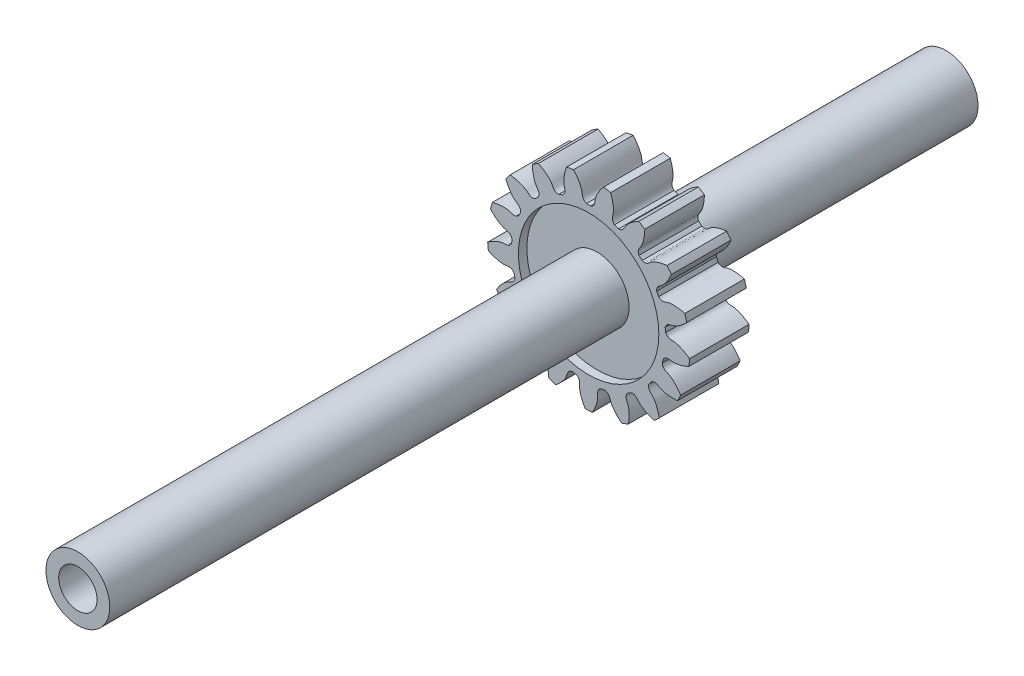
SolidWorks part; units mm, degrees
ref_plane "前视基准面" through (0, 0, 0) normal (0, 0, 1) x (1, 0, 0)
ref_plane "上视基准面" through (0, 0, 0) normal (0, 1, 0) x (1, 0, 0)
ref_plane "右视基准面" through (0, 0, 0) normal (1, 0, 0) x (0, 0, -1)
sketch "草图1" plane through (0, 0, 0) normal (0, 0, 1) x (1, 0, 0)
  circle A0 centre (0, 0) radius 23.75
extrude "凸台-拉伸1" add sketch "草图1" along normal blind 14
ref_axis "基准轴1" through (0, 0, 14) along (0, 0, -1)
sketch "草图2" plane through (0, 0, 0) normal (0, 0, 1) x (1, 0, 0)
  line L0 (0, 0) -> (0, 23.75) construction
  circle A0 centre (0, 0) radius 23.75 construction
  arc A1 (0.5042, 18.118) -> (-0.5042, 18.118) centre (0, 0) ccw
  arc A2 (7.7891, 26.8518) -> (-7.7891, 26.8518) centre (0, 0) ccw
  spline S0 degree 3 poles (0.5042, 18.118) (1.5697, 18.5621) (1.4155, 19.387) (1.5958, 20.1621) (1.6124, 20.2279) (1.6325, 20.301) (1.6564, 20.3815) (1.6842, 20.469) (1.7164, 20.5635) (1.7532, 20.6649) (1.7948, 20.773) (1.8417, 20.8876) (1.894, 21.0086) (1.952, 21.1357) (2.016, 21.2689) (2.0862, 21.408) (2.163, 21.5526) (2.2465, 21.7027) (2.337, 21.8579) (2.4348, 22.0182) (2.54, 22.1832) (2.653, 22.3527) (2.7739, 22.5264) (2.9029, 22.7042) (3.0403, 22.8857) (3.1862, 23.0708) (3.3408, 23.259) (3.5044, 23.4502) (3.6771, 23.644) (3.8591, 23.8402) (4.0505, 24.0385) (4.2515, 24.2385) (4.4622, 24.44) (4.6828, 24.6427) (4.9134, 24.8461) (5.1541, 25.0501) (5.405, 25.2543) (5.6663, 25.4584) (5.9379, 25.6619) (6.2201, 25.8647) (6.5129, 26.0663) (6.8163, 26.2664) (7.2396, 26.5336) (7.5664, 26.7263) (7.7891, 26.8518) knots 0 0 0 0 0.193883 0.199024 0.204851 0.211363 0.21856 0.226443 0.235011 0.244265 0.254205 0.264829 0.27614 0.288136 0.300817 0.314184 0.328236 0.342973 0.358397 0.374505 0.391299 0.408779 0.426944 0.445795 0.465331 0.485552 0.506459 0.528051 0.550329 0.573293 0.596941 0.621276 0.646296 0.672001 0.698392 0.725468 0.753229 0.781677 0.810809 0.840627 0.871131 0.90232 0.934195 1 1 1 1
  spline S1 degree 3 poles (-0.5042, 18.118) (-1.5697, 18.5621) (-1.4155, 19.387) (-1.5958, 20.1621) (-1.6124, 20.2279) (-1.6325, 20.301) (-1.6564, 20.3815) (-1.6842, 20.469) (-1.7164, 20.5635) (-1.7532, 20.6649) (-1.7948, 20.773) (-1.8417, 20.8876) (-1.894, 21.0086) (-1.952, 21.1357) (-2.016, 21.2689) (-2.0862, 21.408) (-2.163, 21.5526) (-2.2465, 21.7027) (-2.337, 21.8579) (-2.4348, 22.0182) (-2.54, 22.1832) (-2.653, 22.3527) (-2.7739, 22.5264) (-2.9029, 22.7042) (-3.0403, 22.8857) (-3.1862, 23.0708) (-3.3408, 23.259) (-3.5044, 23.4502) (-3.6771, 23.644) (-3.8591, 23.8402) (-4.0505, 24.0385) (-4.2515, 24.2385) (-4.4622, 24.44) (-4.6828, 24.6427) (-4.9134, 24.8461) (-5.1541, 25.0501) (-5.405, 25.2543) (-5.6663, 25.4584) (-5.9379, 25.6619) (-6.2201, 25.8647) (-6.5129, 26.0663) (-6.8163, 26.2664) (-7.2396, 26.5336) (-7.5664, 26.7263) (-7.7891, 26.8518) knots 0 0 0 0 0.193883 0.199024 0.204851 0.211363 0.21856 0.226443 0.235011 0.244265 0.254205 0.264829 0.27614 0.288136 0.300817 0.314184 0.328236 0.342973 0.358397 0.374505 0.391299 0.408779 0.426944 0.445795 0.465331 0.485552 0.506459 0.528051 0.550329 0.573293 0.596941 0.621276 0.646296 0.672001 0.698392 0.725468 0.753229 0.781677 0.810809 0.840627 0.871131 0.90232 0.934195 1 1 1 1
extrude "切除-拉伸1" cut sketch "草图2" along normal through all
pattern_circular "阵列(圆周)1" count 17 over 360 about axis through (0, 0, 14) along (0, 0, -1) of "切除-拉伸1"
sketch "草图3" plane through (0, 0, 0) normal (0, 0, 1) x (1, 0, 0)
  circle A0 centre (0, 0) radius 21.25 construction
  dimension "Dn" = 42.5
sketch "草图4" plane through (0, 0, 14) normal (0, 0, 1) x (1, 0, 0)
  circle A0 centre (0, 0) radius 5
  dimension "D1" = 10
extrude "切除-拉伸2" cut sketch "草图4" against normal through all
sketch "草图5" plane through (0, 0, 14) normal (0, 0, 1) x (1, 0, 0)
  circle A0 centre (0, 0) radius 4.5
  circle A1 centre (0, 0) radius 7.5
  dimension "D1" = 15
  dimension "D2" = 9
extrude "凸台-拉伸2" add sketch "草图5" along normal blind 120
sketch "草图6" plane through (0, 0, 0) normal (0, 0, -1) x (-1, 0, 0)
  circle A0 centre (0, 0) radius 4.5
  circle A1 centre (0, 0) radius 7.5
  dimension "D1" = 15
  dimension "D2" = 9
extrude "凸台-拉伸3" add sketch "草图6" along normal blind 70
sketch "草图7" plane through (0, 0, 0) normal (0, 0, -1) x (-1, 0, 0)
  circle A0 centre (0, 0) radius 16.5
  dimension "D1" = 33
extrude "切除-拉伸3" cut sketch "草图7" against normal blind 2
sketch "草图8" plane through (0, 0, 14) normal (0, 0, 1) x (1, 0, 0)
  circle A0 centre (0, 0) radius 16.5
  dimension "D1" = 33
extrude "切除-拉伸4" cut sketch "草图8" against normal blind 2
sketch "草图9" plane through (0, 0, 0) normal (0, 0, 1) x (1, 0, 0)
  circle A0 centre (0, 0) radius 10
  circle A1 centre (0, 0) radius 12.5
sketch "草图10" plane through (0, 0, -70) normal (0, 0, -1) x (-1, 0, 0)
  circle A0 centre (0, 0) radius 10
sketch "草图11" plane through (0, 0, 14) normal (0, 0, -1) x (-1, 0, 0)
  circle A0 centre (0, 0) radius 12.5
  circle A1 centre (0, 0) radius 10
sketch "草图12" plane through (0, 0, 2) normal (0, 0, -1) x (-1, 0, 0)
  circle A0 centre (0, 0) radius 4.5
  circle A1 centre (0, 0) radius 7.5
  dimension "D1" = 15
extrude "凸台-拉伸7" add sketch "草图12" along normal up to next (2 mm away)
sketch "草图13" plane through (0, 0, 12) normal (0, 0, 1) x (1, 0, 0)
  circle A0 centre (0, 0) radius 5
sketch "草图14" plane through (0, 0, 12) normal (0, 0, 1) x (1, 0, 0)
  circle A0 centre (0, 0) radius 5
  circle A1 centre (0, 0) radius 7.5
  dimension "D1" = 15
extrude "凸台-拉伸8" add sketch "草图13" against normal up to surface (10 mm away) up to face at (-4.5, 0, 2)
extrude "凸台-拉伸9" add sketch "草图14" along normal up to next (2 mm away)
sketch "草图15" plane through (0, 0, 134) normal (0, 0, 1) x (1, 0, 0)
  circle A0 centre (0, 0) radius 4.5
extrude "切除-拉伸9" cut sketch "草图15" against normal blind 300
